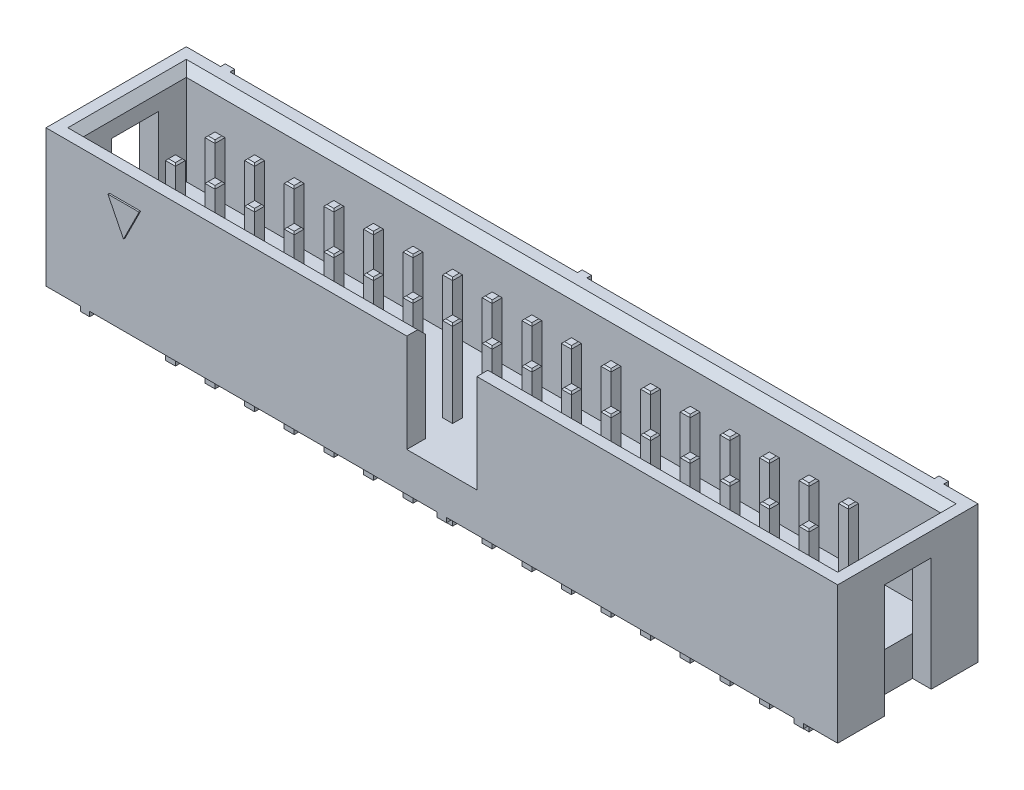
SolidWorks part; units mm, degrees
note: The reader was unsure of these and kept them because the rebuilt part matched: shared geometry of "Sketch1<3>", "Sketch1<4>", "Sketch1<5>".
ref_plane "Front Plane" through (0, 0, 0) normal (0, 0, 1) x (1, 0, 0)
ref_plane "Top Plane" through (0, 0, 0) normal (0, 1, 0) x (1, 0, 0)
ref_plane "Right Plane" through (0, 0, 0) normal (1, 0, 0) x (0, 0, -1)
sketch "Sketch1" plane through (0, 0, 0) normal (0, 1, 0) x (1, 0, 0)
  line L0 (-24.19, 3.3) -> (24.19, 3.3)
  line L1 (-25.39, -4.5) -> (25.39, -4.5)
  line L2 (-25.39, -4.5) -> (-25.39, 4.5)
  line L3 (-25.39, 4.5) -> (25.39, 4.5)
  line L4 (25.39, -4.5) -> (25.39, 4.5)
  line L5 (-25.39, -4.5) -> (25.39, 4.5) construction
  line L6 (-25.39, 4.5) -> (25.39, -4.5) construction
  line L7 (24.19, -3.3) -> (24.19, 3.3)
  line L8 (-24.19, -3.3) -> (24.19, -3.3)
  line L9 (-24.19, -3.3) -> (-24.19, 3.3)
  line L10 (-25.39, 1.5) -> (-24.19, 1.5)
  line L11 (0, 0) -> (-50000, 0) construction
  line L12 (0, 0) -> (0, -50000) construction
  line L13 (-25.39, -1.5) -> (-24.19, -1.5)
  line L14 (-2.25, -3.3) -> (-2.25, -4.5)
  line L15 (2.25, -3.3) -> (2.25, -4.5)
  line L16 (25.39, -1.5) -> (24.19, -1.5)
  line L17 (25.39, 1.5) -> (24.19, 1.5)
  line L18 (-23.19, 4.5) -> (-23.19, 4.8)
  line L19 (-23.19, 4.8) -> (-22.59, 4.8)
  line L20 (-22.59, 4.8) -> (-22.59, 4.5)
  line L21 (-0.3, 4.5) -> (-0.3, 4.8)
  line L22 (-0.3, 4.8) -> (0.3, 4.8)
  line L23 (0.3, 4.8) -> (0.3, 4.5)
  line L24 (22.59, 4.8) -> (22.59, 4.5)
  line L25 (23.19, 4.8) -> (22.59, 4.8)
  line L26 (23.19, 4.5) -> (23.19, 4.8)
  point P0 (0, 0)
  point P38 (-22.89, 4.8)
  dimension "D1" = 9
  dimension "D2" = 50.78
  dimension "D4" = 3
  dimension "D5" = 4.5
  dimension "D6" = 0.6
  dimension "D7" = 2.5
  dimension "D8" = 0.3
  dimension "D3" = 1.2
extrude "Boss-Extrude1" add sketch "Sketch1" along normal blind 8.8 from offset 0.3 contours L17 L4 L3 L2 L10 L9 L0 L7 | L2 L13 L9 L10 | L14 L8 L9 L13 L2 L1 | L15 L8 L14 L1 | L9 L8 L7 L0 | L4 L16 L7 L8 L15 L1 | L4 L17 L7 L16 | L18 L19 L20
extrude "Boss-Extrude2" add sketch "Sketch1<3>" along normal up to surface (9.1 mm away) contours L3 L26 L25 L24 | L23 L22 L21 L3 | L20 L19 L18 L3 up to face at (0, 9.1, 0)
sketch "Sketch1<3>" plane through (0, 0, 0) normal (0, 1, 0) x (1, 0, 0) same geometry as "Sketch1"
extrude "Cut-Extrude1" cut sketch "Sketch1<4>" against normal blind 6.3 from surface at 9.1 contours L9 L8 L7 L0 | L15 L8 L14 L1 starting at face at (0, 9.1, -3.4875)
sketch "Sketch1<4>" plane through (0, 0, 0) normal (0, 1, 0) x (1, 0, 0) same geometry as "Sketch1"
extrude "Cut-Extrude2" cut sketch "Sketch1<5>" along normal blind 7.3 from surface at 0.3 contours L2 L13 L9 L10 | L4 L17 L7 L16 starting at face at (0, 0.3, -2.7)
sketch "Sketch1<5>" plane through (0, 0, 0) normal (0, 1, 0) x (1, 0, 0) same geometry as "Sketch1"
sketch "Sketch3" plane through (0, 0, 4.5) normal (0, 0, 1) x (1, 0, 0)
  line L1 (-23.19, 0) -> (-22.59, 0)
  line L2 (-23.19, 0) -> (-23.19, 0.3)
  line L3 (-23.19, 0.3) -> (-22.59, 0.3)
  line L4 (-22.59, 0) -> (-22.59, 0.3)
  line L5 (-0.3, 0) -> (0.3, 0)
  line L6 (-0.3, 0) -> (-0.3, 0.3)
  line L7 (-0.3, 0.3) -> (0.3, 0.3)
  line L8 (0.3, 0) -> (0.3, 0.3)
  line L9 (22.59, 0) -> (23.19, 0)
  line L10 (22.59, 0) -> (22.59, 0.3)
  line L11 (22.59, 0.3) -> (23.19, 0.3)
  line L12 (23.19, 0) -> (23.19, 0.3)
extrude "Boss-Extrude3" add sketch "Sketch3" against normal through all
chamfer "Chamfer2" distance 0.5 angle 45 5 edges at (13.22, 9.1, 3.3) (24.19, 9.1, 0) (-13.22, 9.1, 3.3) (-24.19, 9.1, 0) (0, 9.1, -3.3)
sketch "Sketch4" plane through (0, 0, 0) normal (0, 1, 0) x (1, 0, 0)
  line L0 (0, 0) -> (-50000, 0) construction
  line L1 (-20.32, 0) -> (-20.32, 50000) construction
  line L2 (-25.39, -4.5) -> (-25.39, 4.5) construction
  line L3 (-20.64, -0.95) -> (-20, -1.59) construction
  line L4 (-20.64, 1.59) -> (-20, 1.59)
  line L5 (-20.64, 1.59) -> (-20.64, 0.95)
  line L6 (-20.64, 0.95) -> (-20, 0.95)
  line L7 (-20, 1.59) -> (-20, 0.95)
  line L8 (-20.64, 1.59) -> (-20, 0.95) construction
  line L9 (-20.64, 0.95) -> (-20, 1.59) construction
  line L10 (-20.64, -1.59) -> (-20, -0.95) construction
  line L11 (-20, -1.59) -> (-20, -0.95)
  line L12 (-20.64, -0.95) -> (-20, -0.95)
  line L13 (-20.64, -1.59) -> (-20.64, -0.95)
  line L14 (-20.64, -1.59) -> (-20, -1.59)
  point P7 (-20.32, 1.27)
  point P16 (-20.32, -1.27)
  dimension "D1" = 5.07
  dimension "D2" = 0.64
  dimension "D3" = 2.54
extrude "Cut-Extrude4" cut sketch "Sketch4" along normal through all
pattern_linear "LPattern1" count 17 spacing 2.54 along (1, 0, 0) of "Cut-Extrude4"
sketch "Sketch6" plane through (0, 0, 4.5) normal (0, 0, 1) x (1, 0, 0)
  line L0 (-21.32, 7.5) -> (-20.32, 5.5)
  line L1 (-20.32, 5.5) -> (-19.32, 7.5)
  line L2 (-19.32, 7.5) -> (-21.32, 7.5)
  line L3 (-25.39, 9.1) -> (-2.25, 9.1) construction
  line L4 (-25.39, 9.1) -> (-25.39, 0.3) construction
  dimension "D1" = 1.6
  dimension "D2" = 2
  dimension "D3" = 2
  dimension "D4" = 5.07
extrude "Boss-Extrude5" add sketch "Sketch6" along normal blind 0.1
sketch "Sketch5" plane through (0, 0, 0) normal (0, 1, 0) x (1, 0, 0)
  line L1 (-20.64, -1.59) -> (-20, -1.59)
  line L2 (-20.64, -1.59) -> (-20.64, -0.95)
  line L3 (-20.64, -0.95) -> (-20, -0.95)
  line L4 (-20, -1.59) -> (-20, -0.95)
extrude "Boss-Extrude4" add sketch "Sketch5" along normal blind 8.3 and the other way blind 3 separate body
chamfer "Chamfer3" distance 0.1 angle 45 8 edges at (-20.32, -3, 1.59) (-20, -3, 1.27) (-20.32, -3, 0.95) (-20.64, -3, 1.27) (-20.32, 8.3, 0.95) (-20, 8.3, 1.27) (-20.32, 8.3, 1.59) (-20.64, 8.3, 1.27)
pattern_linear "LPattern3" count 17 spacing 2.54 along (1, 0, 0) count 2 spacing 2.54 along (0, 0, -1) of bodies 111
